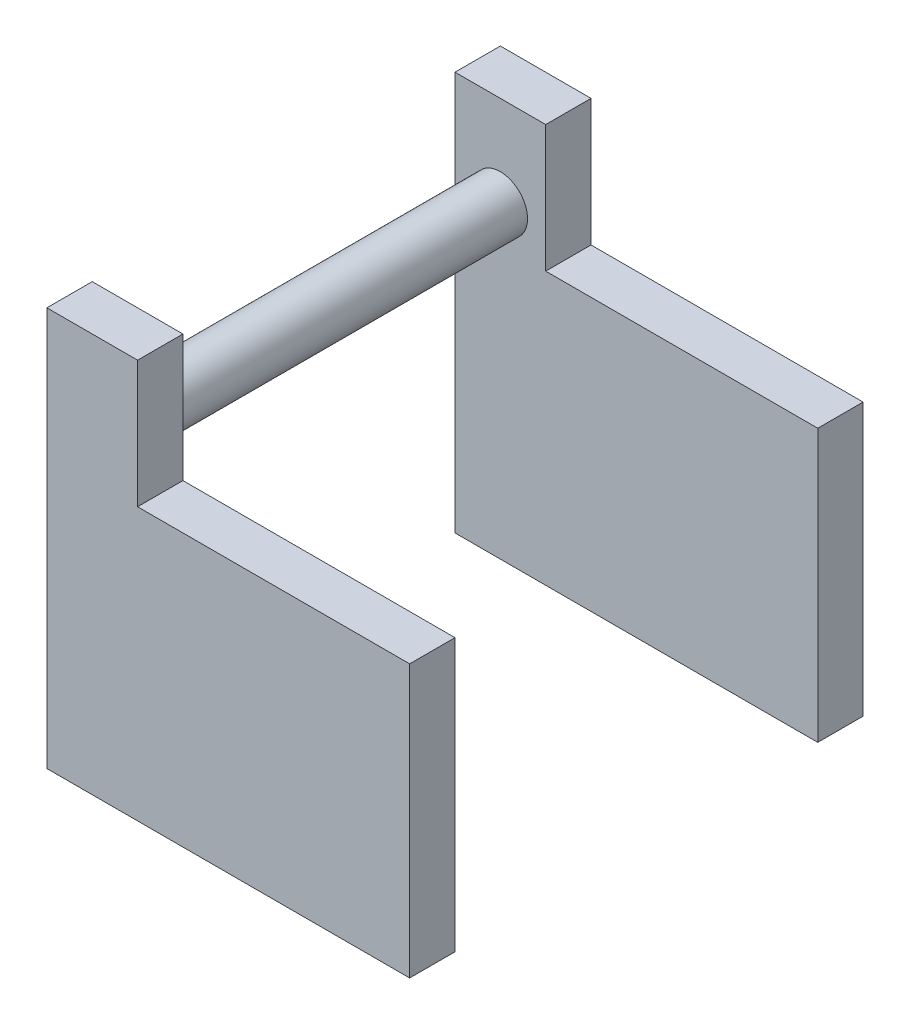
SolidWorks part; units mm, degrees
ref_plane "Front Plane" through (0, 0, 0) normal (0, 0, 1) x (1, 0, 0)
ref_plane "Top Plane" through (0, 0, 0) normal (0, 1, 0) x (1, 0, 0)
ref_plane "Right Plane" through (0, 0, 0) normal (1, 0, 0) x (0, 0, -1)
sketch "Sketch1" plane through (0, 0, 0) normal (0, 0, 1) x (1, 0, 0)
  line L1 (0, 0) -> (-25.4, 0)
  line L2 (0, 0) -> (0, 19.05)
  line L3 (0, 19.05) -> (-19.05, 19.05)
  line L4 (-25.4, 0) -> (-25.4, 6.35)
  line L6 (-25.4, 6.35) -> (-25.4, 27.94)
  line L7 (-25.4, 27.94) -> (-19.05, 27.94)
  line L8 (-19.05, 19.05) -> (-19.05, 27.94)
  dimension "D1" = 25.4
  dimension "D2" = 21.59
  dimension "D3" = 19.05
  dimension "D4" = 6.35
extrude "Boss-Extrude1" add sketch "Sketch1" along normal blind 31.75
sketch "Sketch2" plane through (0, 27.94, 0) normal (0, 1, 0) x (1, 0, 0)
  line L0 (-25.4, -31.75) -> (-25.4, 0) construction
  line L1 (-25.4, -3.175) -> (0, -3.175)
  line L2 (-25.4, -3.175) -> (-25.4, -28.575)
  line L3 (-25.4, -28.575) -> (0, -28.575)
  line L4 (0, -3.175) -> (0, -28.575)
  line L5 (0, -31.75) -> (0, 0) construction
  line L6 (-19.05, -31.75) -> (-25.4, -31.75) construction
  dimension "D1" = 25.4
  dimension "D2" = 3.175
extrude "Cut-Extrude1" cut sketch "Sketch2" against normal up to surface (27.94 mm away) up to face at (-12.7, 0, 15.875)
sketch "Sketch3" plane through (0, 0, 3.175) normal (0, 0, 1) x (1, 0, 0)
  line L0 (-25.4, 0) -> (-25.4, 27.94) construction
  line L1 (-19.05, 27.94) -> (-25.4, 27.94) construction
  circle A0 centre (-22.225, 21.59) radius 1.905
  dimension "D1" = 3.81
  dimension "D2" = 3.175
  dimension "D3" = 6.35
extrude "Boss-Extrude2" add sketch "Sketch3" along normal up to surface (25.4 mm away) up to face at (-14.8167, 15.6633, 28.575)
